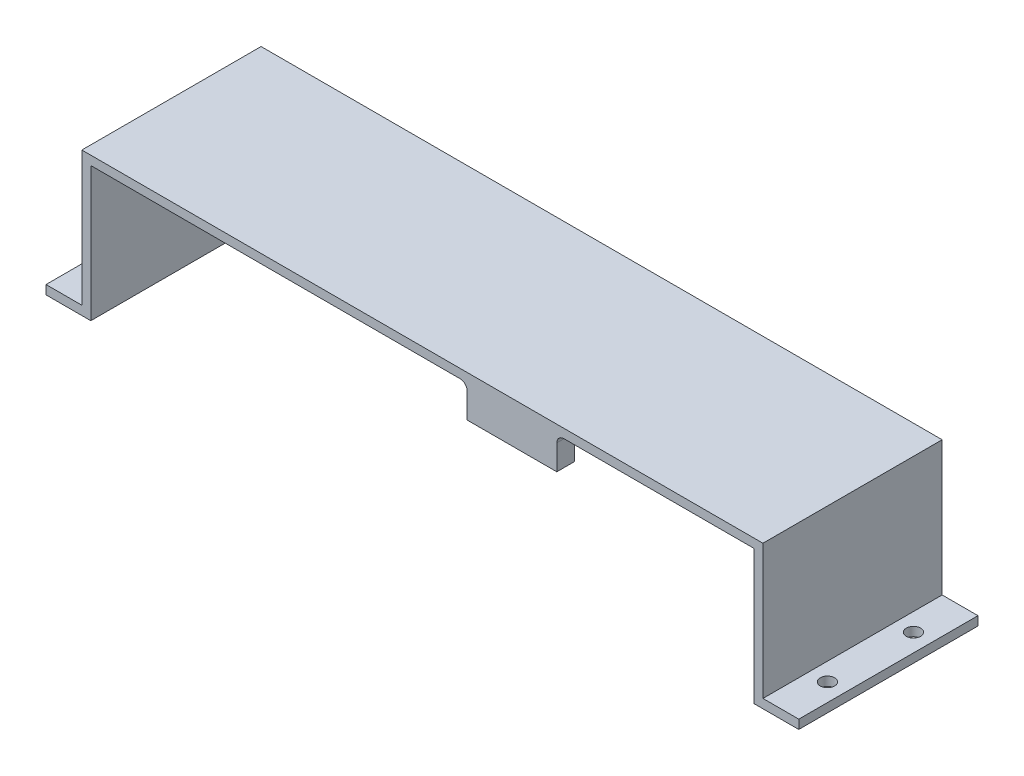
SolidWorks part; units mm, degrees
other "Markup1"
sketch "Sketch8" plane through (104.775, 3.175, 31.75) normal (0.0545, 0.0227, 0.9983) x (-0.9792, -0.1942, 0.0579)
ref_plane "Front Plane" through (0, 0, 0) normal (0, 0, 1) x (1, 0, 0)
ref_plane "Top Plane" through (0, 0, 0) normal (0, 1, 0) x (1, 0, 0)
ref_plane "Right Plane" through (0, 0, 0) normal (1, 0, 0) x (0, 0, -1)
sketch "Sketch1" plane through (0, 0, 0) normal (0, 1, 0) x (1, 0, 0)
  line L1 (-117.475, 31.75) -> (117.475, 31.75)
  line L2 (-117.475, 31.75) -> (-117.475, -31.75)
  line L3 (-117.475, -31.75) -> (117.475, -31.75)
  line L4 (117.475, 31.75) -> (117.475, -31.75)
  line L5 (-117.475, 31.75) -> (117.475, -31.75) construction
  line L6 (-117.475, -31.75) -> (117.475, 31.75) construction
  point P0 (0, 0)
  dimension "D1" = 234.95
  dimension "D2" = 63.5
extrude "Boss-Extrude1" add sketch "Sketch1" along normal blind 3.175
sketch "Sketch3" plane through (0, 3.175, 0) normal (0, 1, 0) x (1, 0, 0)
  line L0 (-117.475, -31.75) -> (117.475, -31.75) construction
  line L1 (-117.475, 31.75) -> (-120.65, 31.75)
  line L2 (-117.475, 31.75) -> (-117.475, -31.75)
  line L3 (-117.475, -31.75) -> (-120.65, -31.75)
  line L4 (-120.65, 31.75) -> (-120.65, -31.75)
  line L5 (0, -55) -> (0, 55) construction
  line L6 (117.475, -31.75) -> (120.65, -31.75)
  line L7 (120.65, 31.75) -> (120.65, -31.75)
  line L8 (117.475, 31.75) -> (120.65, 31.75)
  line L9 (117.475, 31.75) -> (117.475, -31.75)
  dimension "D1" = 3.175
extrude "Boss-Extrude2" add sketch "Sketch3" against normal blind 50.8
sketch "Sketch4" plane through (120.65, 0, 0) normal (1, 0, 0) x (0, 0, -1)
  line L0 (31.75, -47.625) -> (31.75, 3.175) construction
  line L1 (-31.75, -47.625) -> (31.75, -47.625)
  line L2 (-31.75, -47.625) -> (-31.75, -44.45)
  line L3 (-31.75, -44.45) -> (31.75, -44.45)
  line L4 (31.75, -47.625) -> (31.75, -44.45)
  dimension "D1" = 3.175
extrude "Boss-Extrude3" add sketch "Sketch4" along normal blind 12.7
sketch "Sketch5" plane through (0, -47.625, 0) normal (0, -1, 0) x (1, 0, 0)
  line L1 (133.35, -31.75) -> (117.475, -31.75) construction
  line L3 (117.475, 0) -> (133.35, 0) construction
  line L4 (117.475, 31.75) -> (117.475, -31.75) construction
  line L5 (133.35, 31.75) -> (133.35, -31.75) construction
  circle A0 centre (127, -15.24) radius 2.54
  circle A1 centre (127, 15.24) radius 2.54
  dimension "D1" = 5.08
  dimension "D2" = 6.35
  dimension "D3" = 16.51
extrude "Cut-Extrude1" cut sketch "Sketch5" against normal blind 12.7
mirror "Mirror1" about plane through (0, 0, 0) normal (1, 0, 0) of "Boss-Extrude3", "Cut-Extrude1"
sketch "Sketch6" plane through (0, 0, 31.75) normal (0, 0, 1) x (1, 0, 0)
  line L14 (-117.475, 0) -> (117.475, 0) construction
  line L15 (15.875, 0) -> (47.625, 0)
  line L16 (15.875, 0) -> (15.875, -11.43)
  line L17 (15.875, -11.43) -> (47.625, -11.43)
  line L18 (47.625, 0) -> (47.625, -11.43)
  line L19 (-117.475, -47.625) -> (-117.475, 0) construction
  dimension "D1" = 11.43
  dimension "D2" = 31.75
  dimension "D3" = 165.1
extrude "Boss-Extrude4" add sketch "Sketch6" against normal blind 6.35
fillet "Fillet1" radius 2.54 2 edges at (47.625, 0, 28.575) (15.875, 0, 28.575)
